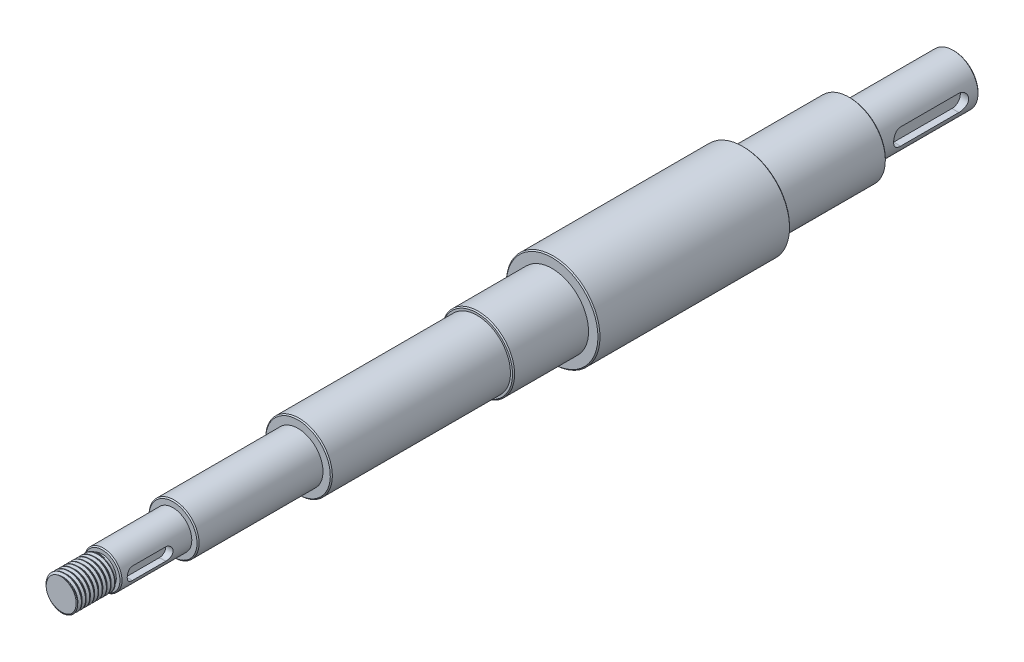
SolidWorks part; units mm, degrees
material "Malleable Cast Iron"
ref_plane "Front Plane" through (0, 0, 0) normal (0, 0, 1) x (1, 0, 0)
ref_plane "Top Plane" through (0, 0, 0) normal (0, 1, 0) x (1, 0, 0)
ref_plane "Right Plane" through (0, 0, 0) normal (1, 0, 0) x (0, 0, -1)
sketch "Sketch1" plane through (0, 0, 0) normal (1, 0, 0) x (0, 0, -1)
  line L0 (214.5, 0) -> (-214.5, 0) construction
  line L1 (214.5, 0) -> (214.5, 12)
  line L2 (214.5, 12) -> (164.5, 12)
  line L3 (164.5, 12) -> (164.5, 17.5)
  line L4 (164.5, 17.5) -> (113.5, 17.5)
  line L5 (113.5, 17.5) -> (113.5, 22.5)
  line L6 (113.5, 22.5) -> (21.5, 22.5)
  line L8 (21.5, 17.5) -> (-14.5, 17.5)
  line L9 (-14.5, 17.5) -> (-14.5, 16)
  line L10 (-14.5, 16) -> (-100.5, 16)
  line L11 (-100.5, 16) -> (-100.5, 12)
  line L12 (-100.5, 12) -> (-160.5, 12)
  line L13 (-160.5, 12) -> (-160.5, 9)
  line L14 (-160.5, 9) -> (-194.5, 9)
  line L16 (-195.5, 8) -> (-214.5, 8)
  line L17 (-214.5, 8) -> (-214.5, 0)
  line L18 (-214.5, 0) -> (214.5, 0)
  line L19 (21.5, 22.5) -> (21.5, 17.5)
  line L20 (214.5, 0) -> (248.6672, 0) construction
  line L21 (-195.5, 6.75) -> (-194.5, 6.75)
  line L23 (-195.5, 8) -> (-195.5, 6.75)
  line L24 (-194.5, 9) -> (-194.5, 6.75)
  point P3 (0, 0)
  dimension "D1" = 429
  dimension "D2" = 50
  dimension "D3" = 51
  dimension "D4" = 92
  dimension "D5" = 36
  dimension "D6" = 86
  dimension "D7" = 60
  dimension "D8" = 1
  dimension "D9" = 24
  dimension "D10" = 35
  dimension "D11" = 45
  dimension "D12" = 35
  dimension "D13" = 32
  dimension "D14" = 24
  dimension "D15" = 18
  dimension "D16" = 16
  dimension "D17" = 13.5
revolve "Revolve1" add sketch "Sketch1" angle 360 about L20
chamfer "Chamfer1" distance 0.5 angle 45 9 edges at (0, -17.5, -164.5) (0, -8, 214.5) (0, -12, 160.5) (0, -16, 100.5) (0, -17.5, 14.5) (0, -22.5, -21.5) (0, -22.5, -113.5) (0, -12, -214.5) (0, -9, 194.5)
thread "Thread1" pitch 2 start angle 0, offset 5, length 30, pitch 2, diameter 16
ref_plane "Plane1" through (8, 0, 190.5) normal (0, -1, 0) x (1, 0, 0)
sketch "Thread Profile1" plane through (8, 0, 190.5) normal (0, -1, 0) x (1, 0, 0)
  line L0 (0, 0) -> (0, 2) construction
  line L11 (0, 0) -> (0, 1.75)
  line L12 (0, 1.75) -> (-1.0825, 1.125)
  line L13 (-1.0825, 1.125) -> (-1.0825, 0.625)
  line L15 (-1.0825, 0.625) -> (0, 0)
  line L17 (-1.0825, 0.875) -> (0, 0.875) construction
  point P2 (0, 0)
  dimension "Pitch" = 2
  dimension "Profile_Angle" = 60
  dimension "Profile_Land" = 0.5
  dimension "Profile_Height" = 1.0825
ref_plane "Plane2" through (9, 0, 0) normal (1, 0, 0) x (0, 0, -1)
sketch "Sketch6" plane through (9, 0, 0) normal (1, 0, 0) x (0, 0, -1)
  line L0 (-188.5, 0) -> (-172.5, 0) construction
  line L1 (-188.5, 3) -> (-172.5, 3)
  line L2 (-188.5, -3) -> (-172.5, -3)
  line L3 (-194.5, 8.5) -> (-194.5, -8.5) construction
  arc A0 (-188.5, 3) -> (-188.5, -3) centre (-188.5, 0) ccw
  arc A1 (-172.5, -3) -> (-172.5, 3) centre (-172.5, 0) ccw
  point P3 (-180.5, 0)
  dimension "D1" = 3
  dimension "D2" = 6
  dimension "D3" = 16
extrude "Cut-Extrude1" cut sketch "Sketch6" against normal blind 3.5
ref_plane "Plane3" through (12, 0, 0) normal (1, 0, 0) x (0, 0, -1)
sketch "Sketch7" plane through (12, 0, 0) normal (1, 0, 0) x (0, 0, -1)
  line L0 (177.5, 0) -> (205.5, 0) construction
  line L1 (177.5, 4) -> (205.5, 4)
  line L2 (177.5, -4) -> (205.5, -4)
  line L3 (214.5, -11.5) -> (214.5, 11.5) construction
  arc A0 (177.5, 4) -> (177.5, -4) centre (177.5, 0) ccw
  arc A1 (205.5, -4) -> (205.5, 4) centre (205.5, 0) ccw
  point P3 (191.5, 0)
  dimension "D1" = 4
  dimension "D2" = 9
  dimension "D3" = 28
extrude "Cut-Extrude2" cut sketch "Sketch7" against normal blind 4
